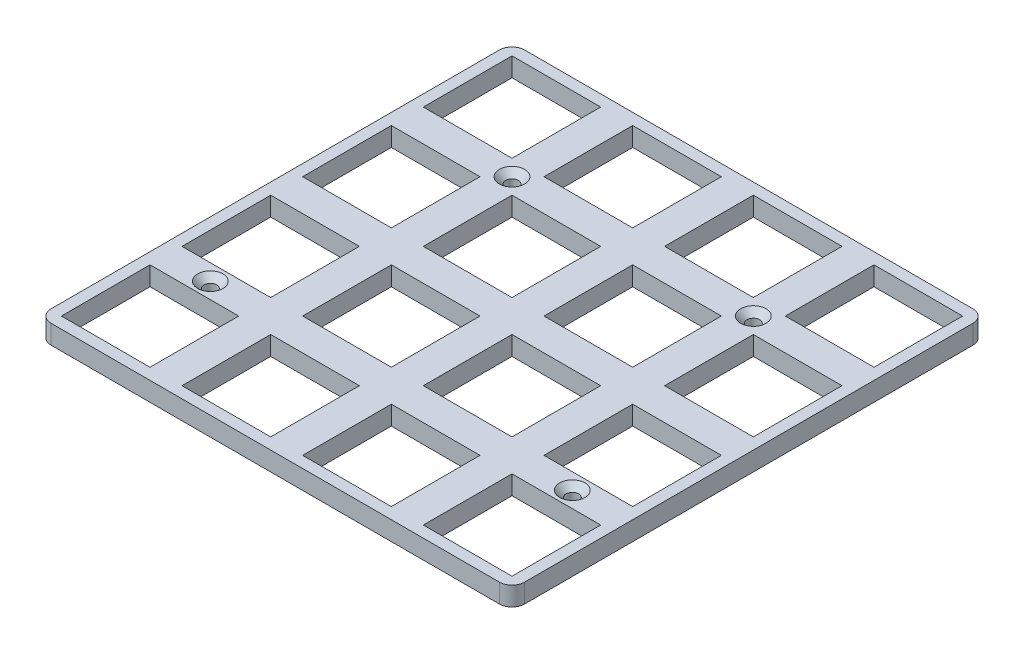
SolidWorks part; units mm, degrees
ref_plane "Front Plane" through (0, 0, 0) normal (0, 0, 1) x (1, 0, 0)
ref_plane "Top Plane" through (0, 0, 0) normal (0, 1, 0) x (1, 0, 0)
ref_plane "Right Plane" through (0, 0, 0) normal (1, 0, 0) x (0, 0, -1)
sketch "Sketch5" plane through (0, 0, 0) normal (1, 0, 0) x (0, 0, -1)
  line L0 (0, 0) -> (0, 13.4604) construction
sketch "Sketch1" plane through (0, 0, 0) normal (0, 1, 0) x (1, 0, 0)
  line L5 (-16.525, 21.575) -> (-16.525, 35.575)
  line L6 (-37.575, -37.575) -> (37.575, -37.575)
  line L11 (-37.575, -37.575) -> (-37.575, 37.575)
  line L12 (-37.575, 37.575) -> (37.575, 37.575)
  line L72 (37.575, -37.575) -> (37.575, 37.575)
  line L88 (-37.575, -37.575) -> (37.575, 37.575) construction
  line L89 (-37.575, 37.575) -> (37.575, -37.575) construction
  line L90 (-35.575, 21.575) -> (-21.575, 21.575)
  line L91 (-35.575, 21.575) -> (-35.575, 35.575)
  line L92 (-35.575, 35.575) -> (-21.575, 35.575)
  line L93 (-21.575, 21.575) -> (-21.575, 35.575)
  line L94 (-35.575, 21.575) -> (-21.575, 35.575) construction
  line L95 (-35.575, 35.575) -> (-21.575, 21.575) construction
  line L96 (-16.525, 21.575) -> (-2.525, 21.575)
  line L97 (-2.525, 21.575) -> (-2.525, 35.575)
  line L98 (-16.525, 35.575) -> (-2.525, 35.575)
  line L99 (2.525, 21.575) -> (2.525, 35.575)
  line L100 (2.525, 21.575) -> (16.525, 21.575)
  line L101 (16.525, 21.575) -> (16.525, 35.575)
  line L102 (2.525, 35.575) -> (16.525, 35.575)
  line L103 (21.575, 21.575) -> (21.575, 35.575)
  line L104 (21.575, 21.575) -> (35.575, 21.575)
  line L105 (35.575, 21.575) -> (35.575, 35.575)
  line L106 (21.575, 35.575) -> (35.575, 35.575)
  line L107 (-16.525, 2.525) -> (-16.525, 16.525)
  line L108 (-16.525, 2.525) -> (-2.525, 2.525)
  line L109 (-2.525, 2.525) -> (-2.525, 16.525)
  line L110 (-16.525, 16.525) -> (-2.525, 16.525)
  line L111 (2.525, 2.525) -> (2.525, 16.525)
  line L112 (2.525, 2.525) -> (16.525, 2.525)
  line L113 (16.525, 2.525) -> (16.525, 16.525)
  line L114 (2.525, 16.525) -> (16.525, 16.525)
  line L115 (21.575, 2.525) -> (21.575, 16.525)
  line L116 (21.575, 2.525) -> (35.575, 2.525)
  line L117 (35.575, 2.525) -> (35.575, 16.525)
  line L118 (21.575, 16.525) -> (35.575, 16.525)
  line L119 (-16.525, -16.525) -> (-16.525, -2.525)
  line L120 (-16.525, -16.525) -> (-2.525, -16.525)
  line L121 (-2.525, -16.525) -> (-2.525, -2.525)
  line L122 (-16.525, -2.525) -> (-2.525, -2.525)
  line L123 (2.525, -16.525) -> (2.525, -2.525)
  line L124 (2.525, -16.525) -> (16.525, -16.525)
  line L125 (16.525, -16.525) -> (16.525, -2.525)
  line L126 (2.525, -2.525) -> (16.525, -2.525)
  line L127 (21.575, -16.525) -> (21.575, -2.525)
  line L128 (21.575, -16.525) -> (35.575, -16.525)
  line L129 (35.575, -16.525) -> (35.575, -2.525)
  line L130 (21.575, -2.525) -> (35.575, -2.525)
  line L131 (-16.525, -35.575) -> (-16.525, -21.575)
  line L132 (-16.525, -35.575) -> (-2.525, -35.575)
  line L133 (-2.525, -35.575) -> (-2.525, -21.575)
  line L134 (-16.525, -21.575) -> (-2.525, -21.575)
  line L135 (2.525, -35.575) -> (2.525, -21.575)
  line L136 (2.525, -35.575) -> (16.525, -35.575)
  line L137 (16.525, -35.575) -> (16.525, -21.575)
  line L138 (2.525, -21.575) -> (16.525, -21.575)
  line L139 (21.575, -35.575) -> (21.575, -21.575)
  line L140 (21.575, -35.575) -> (35.575, -35.575)
  line L141 (35.575, -35.575) -> (35.575, -21.575)
  line L142 (21.575, -21.575) -> (35.575, -21.575)
  line L143 (-35.575, 2.525) -> (-35.575, 16.525)
  line L144 (-35.575, 2.525) -> (-21.575, 2.525)
  line L145 (-21.575, 2.525) -> (-21.575, 16.525)
  line L146 (-35.575, 16.525) -> (-21.575, 16.525)
  line L147 (-35.575, -16.525) -> (-35.575, -2.525)
  line L148 (-35.575, -16.525) -> (-21.575, -16.525)
  line L149 (-21.575, -16.525) -> (-21.575, -2.525)
  line L150 (-35.575, -2.525) -> (-21.575, -2.525)
  line L151 (-35.575, -35.575) -> (-35.575, -21.575)
  line L152 (-35.575, -35.575) -> (-21.575, -35.575)
  line L153 (-21.575, -35.575) -> (-21.575, -21.575)
  line L154 (-35.575, -21.575) -> (-21.575, -21.575)
  line L155 (-35.575, 21.575) -> (-16.525, 21.575) construction
  line L156 (-35.575, 21.575) -> (-35.575, 2.525) construction
  point P0 (0, 0)
  point P6 (-28.575, 28.575)
  dimension "D1" = 2
  dimension "D2" = 14
  dimension "D5" = 90
  dimension "D6" = 19.05
  dimension "D7" = 19.05
  dimension "D3" = 4
  dimension "D8" = 75.15
  dimension "D9" = 5.05
  dimension "D10" = 71.15
  dimension "D4" = 4
extrude "Boss-Extrude1" add sketch "Sketch1" along normal blind 3
sketch "Sketch2" plane through (0, 3, 0) normal (0, 1, 0) x (1, 0, 0)
  line L0 (-28.575, -16.525) -> (-28.575, -21.575) construction
  line L5 (-35.575, -16.525) -> (-21.575, -16.525) construction
  line L7 (-21.575, -21.575) -> (-35.575, -21.575) construction
  line L8 (-28.575, -19.05) -> (0, -19.05) construction
  line L9 (-21.575, 16.525) -> (-16.525, 16.525) construction
  line L10 (-21.575, 16.525) -> (-21.575, 21.575) construction
  line L11 (-21.575, 21.575) -> (-16.525, 21.575) construction
  line L12 (-16.525, 16.525) -> (-16.525, 21.575) construction
  line L15 (-21.575, 16.525) -> (-16.525, 21.575) construction
  line L20 (-21.575, 21.575) -> (-16.525, 16.525) construction
  line L22 (-19.05, 19.05) -> (0, 19.05) construction
  circle A0 centre (-19.05, 19.05) radius 1
  circle A1 centre (-28.575, -19.05) radius 1
  point P8 (-19.05, 19.05)
  point P17 (-28.575, -19.05)
  dimension "D1" = 2
  dimension "D2" = 2
  dimension "D3" = 19.05
  dimension "D4" = 28.575
extrude "Cut-Extrude1" cut sketch "Sketch2" against normal up to surface (3 mm away) up to face at (0, 0, 0)
sketch "Sketch3" plane through (0, 3, 0) normal (0, 1, 0) x (1, 0, 0)
  circle A2 centre (-19.05, 19.05) radius 2
  circle A3 centre (-19.05, 19.05) radius 2
  circle A4 centre (-28.575, -19.05) radius 2
  circle A5 centre (-28.575, -19.05) radius 2
  dimension "D1" = 1
  dimension "D2" = 1
extrude "Cut-Extrude2" [suppressed] cut sketch "Sketch3" against normal blind 1
chamfer "Chamfer1" distance 1 angle 45 2 edges at (-19.05, 3, -18.05) (-28.575, 3, 20.05)
mirror "Mirror1" about plane through (0, 0, 0) normal (1, 0, 0) of "Chamfer1", "Cut-Extrude1"
other "Move Face1" flip direction yes face at (37.575, 1.5, 0) face at (0, 1.5, -37.575) face at (0, 1.5, 37.575) face at (-37.575, 1.5, 0) offset 0.2 parameters "D1"=0.2
fillet "Fillet1" radius 2 4 edges at (-37.375, 1.5, -37.375) (37.375, 1.5, -37.375) (37.375, 1.5, 37.375) (-37.375, 1.5, 37.375)
equation "\"screwhole\"=2"
equation "\"D2@Sketch2\"=\"screwhole\""
equation "\"D1@Sketch2\"=\"screwhole\""
